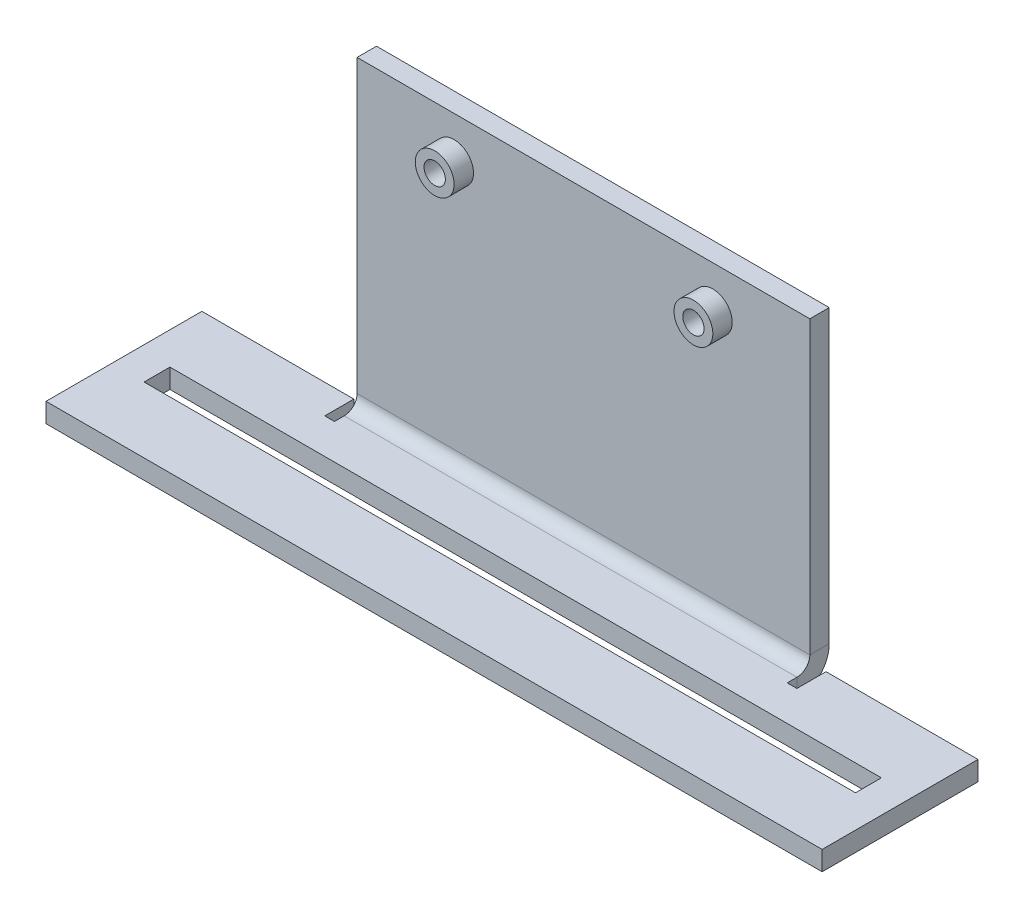
SolidWorks part; units mm, degrees
note: The reader was unsure of these and kept them because the rebuilt part matched: flange length of "边线-法兰2".
ref_plane "前视基准面" through (0, 0, 0) normal (0, 0, 1) x (1, 0, 0)
ref_plane "上视基准面" through (0, 0, 0) normal (0, 1, 0) x (1, 0, 0)
ref_plane "右视基准面" through (0, 0, 0) normal (1, 0, 0) x (0, 0, -1)
other "Configuration Table"
sketch "草图3" plane through (0, 0, 0) normal (0, 1, 0) x (1, 0, 0)
  line L1 (0, 0) -> (70, 0)
  line L2 (0, 0) -> (0, 24)
  line L3 (0, 24) -> (70, 24)
  line L4 (70, 0) -> (70, 24)
sketch "草图15" plane through (0, 0, 0) normal (0, 1, 0) x (1, 0, 0)
  line L0 (0, -41.7521) -> (120, -41.7521)
  line L1 (120, -41.7521) -> (120, -17.6521)
  line L2 (120, -17.6521) -> (95, -17.6521)
  line L3 (95, -17.6521) -> (95, -15.6521)
  line L4 (95, -15.6521) -> (25, -15.6521)
  line L5 (25, -15.6521) -> (25, -17.6521)
  line L6 (25, -17.6521) -> (0, -17.6521)
  line L7 (0, -17.6521) -> (0, -41.7521)
  point P2 (0, 0)
  point P9 (0, 0)
  point P10 (0, 0)
  point P11 (0, 0)
  point P12 (0, 0)
  dimension "D1" = 120
  dimension "D2" = 70
  dimension "D3" = 25
  dimension "D4" = 25
  dimension "D5" = 24.1
  dimension "D6" = 2
  dimension "D7" = 24.1
base flange "基体-法兰2" sketch "草图15" thickness 3 reverse thickness direction no parameters "D1"=0.7366
edge flange "边线-法兰2" sketch "草图20" flange angle 90 flange length 50 flange position material inside bend radius 2 thickness 3 relief rectangular parameters "D6"=10
sketch "草图20" plane through (0, 0, 15.6521) normal (0, 0, -1) x (-1, 0, 0)
  line L0 (-95, 0) -> (-25, 0) construction
  line L1 (-95, 0) -> (-25, 0)
  line L2 (-95, 0) -> (-95, 47)
  line L3 (-95, 47) -> (-25, 47)
  line L4 (-25, 47) -> (-25, 0)
  dimension "D1" = 47
bend "边线折弯2" bend radius 2 bend angle 90 parameters "D5"=1
sketch3d "3D草图1"
  point P0 (35.4576, 40.4576, 18.6521)
sketch "草图21" plane through (0, 0, 0) normal (0, 1, 0) x (1, 0, 0)
  line L1 (5, -27.5883) -> (115, -27.5883)
  line L2 (5, -27.5883) -> (5, -31.5883)
  line L3 (5, -31.5883) -> (115, -31.5883)
  line L4 (115, -27.5883) -> (115, -31.5883)
  dimension "D2" = 110
  dimension "D3" = 4
extrude "切除-拉伸1" cut sketch "草图21" against normal blind 30 normal cut yes
sketch "草图23" plane through (0, 0, 18.6521) normal (0, 0, 1) x (1, 0, 0)
  line L0 (60, 47) -> (60, 2) construction
  line L1 (25, 47) -> (95, 47) construction
  line L2 (95, 2) -> (25, 2) construction
  line L3 (25, 24.5) -> (95, 24.5) construction
  line L4 (25, 2) -> (25, 47) construction
  line L5 (95, 47) -> (95, 2) construction
  line L6 (40, 47) -> (40, 2) construction
  line L7 (80, 47) -> (80, 2) construction
  line L8 (25, 40.5) -> (95, 40.5) construction
  circle A0 centre (40, 40.5) radius 3
  circle A1 centre (80, 40.5) radius 3
  point P20 (0, 0)
  point P21 (0, 0)
  dimension "D4" = 6
  dimension "D1" = 20
  dimension "D2" = 20
  dimension "D3" = 16
extrude "凸台-拉伸1" add sketch "草图23" along normal blind 3
sketch "草图24" plane through (0, 0, 21.6521) normal (0, 0, 1) x (1, 0, 0)
  line L0 (40, 40.5) -> (80, 40.5) construction
  circle A0 centre (40, 40.5) radius 1.65
  circle A2 centre (80, 40.5) radius 1.65
  dimension "D1" = 3.3
  dimension "D3" = 40
  dimension "D2" = 2
extrude "切除-拉伸2" cut sketch "草图24" against normal blind 6 normal cut yes
sketch "折弯-线1" plane through (0, 0, 0) normal (0, 1, 0) x (1, 0, 0)
sketch "边界框1" plane through (0, 0, 0) normal (0, 1, 0) x (1, 0, 0)
sheet metal parameters "钣金8" thickness 3 parameters "D1"=0.7366
flat pattern "平板型式8" [suppressed]
sketch "折弯-线3" plane through (0, 0, 0) normal (0, 1, 0) x (1, 0, 0)
sketch "边界框3" [suppressed] plane through (0, 0, 0) normal (0, 1, 0) x (1, 0, 0)
sheet metal parameters "钣金9" thickness 3 parameters "D1"=0.7366
flat pattern "平板型式8" [suppressed]
sketch "折弯-线3" plane through (0, 0, 0) normal (0, 1, 0) x (1, 0, 0)
sketch "边界框3" [suppressed] plane through (0, 0, 0) normal (0, 1, 0) x (1, 0, 0)
bend of the flat pattern "展平-<边线折弯2>1"
sheet metal parameters "钣金11" thickness 3 parameters "D1"=0.7366
flat pattern "平板型式8" [suppressed]
sketch "折弯-线3" plane through (0, 0, 0) normal (0, 1, 0) x (1, 0, 0)
sketch "边界框3" [suppressed] plane through (0, 0, 0) normal (0, 1, 0) x (1, 0, 0)
bend of the flat pattern "展平-<边线折弯2>1"
sheet metal parameters "钣金15" thickness 3 parameters "D1"=0.7366
flat pattern "平板型式8" [suppressed]
sketch "折弯-线3" plane through (0, 0, 0) normal (0, 1, 0) x (1, 0, 0)
sketch "边界框3" [suppressed] plane through (0, 0, 0) normal (0, 1, 0) x (1, 0, 0)
bend of the flat pattern "展平-<边线折弯2>1"
sheet metal parameters "钣金16" thickness 3 parameters "D1"=0.7366
flat pattern "平板型式8" [suppressed]
sketch "折弯-线3" plane through (0, 0, 0) normal (0, 1, 0) x (1, 0, 0)
sketch "边界框3" [suppressed] plane through (0, 0, 0) normal (0, 1, 0) x (1, 0, 0)
bend of the flat pattern "展平-<边线折弯2>1"
